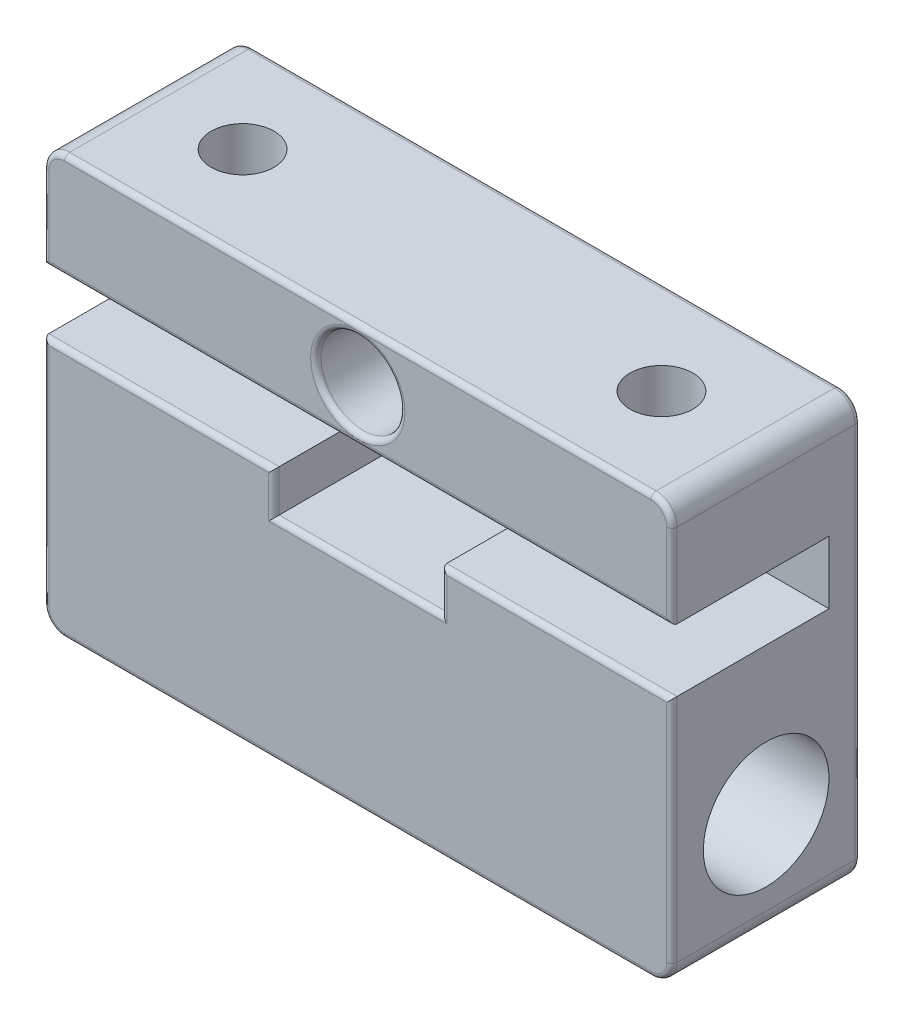
SolidWorks part; units mm, degrees
ref_plane "Front Plane" through (0, 0, 0) normal (0, 0, 1) x (1, 0, 0)
ref_plane "Top Plane" through (0, 0, 0) normal (0, 1, 0) x (1, 0, 0)
ref_plane "Right Plane" through (0, 0, 0) normal (1, 0, 0) x (0, 0, -1)
sketch "Sketch1" plane through (0, 0, 0) normal (0, 0, 1) x (1, 0, 0)
  line L1 (-30, 20) -> (30, 20)
  line L2 (-30, 20) -> (-30, -20)
  line L3 (-30, -20) -> (30, -20)
  line L4 (30, 20) -> (30, -20)
  line L5 (-30, 20) -> (30, -20) construction
  line L6 (-30, -20) -> (30, 20) construction
  point P0 (0, 0)
  dimension "D1" = 40
  dimension "D2" = 60
extrude "Boss-Extrude1" add sketch "Sketch1" along normal mid plane 18
sketch "Sketch2" plane through (-30, 0, 0) normal (-1, 0, 0) x (0, 0, 1)
  line L0 (0, 1.8022) -> (0, -4.9662) construction
  circle A0 centre (0, -10) radius 6
  dimension "D1" = 12
  dimension "D2" = 10
extrude "Cut-Extrude1" cut sketch "Sketch2" against normal through all
sketch "Sketch3" plane through (0, 0, 9) normal (0, 0, 1) x (1, 0, 0)
  line L0 (0, 0) -> (0, 7.3584) construction
  line L4 (30, -20) -> (30, 20)
  line L6 (30, -20) -> (30, 20)
  line L12 (30, 20) -> (-30, 20)
  line L15 (30, 20) -> (-30, 20)
  line L16 (-30, 20) -> (-30, -20)
  line L17 (-30, 20) -> (-30, -20)
  line L18 (-30, -20) -> (30, -20)
  line L19 (-30, -20) -> (30, -20)
  circle A0 centre (0, 15) radius 4
  dimension "D2" = 8
  dimension "D3" = 15
  dimension "D1" = 0
extrude "Cut-Extrude2" cut sketch "Sketch3" against normal through all contours A0 | A0 region at (0, 15, 9)
sketch "Sketch4" plane through (0, 0, 9) normal (0, 0, 1) x (1, 0, 0)
  line L0 (-30, 20) -> (-30, -20) construction
  line L1 (-30, 10) -> (30, 10)
  line L2 (-30, 10) -> (-30, 4)
  line L3 (-30, 4) -> (-8, 4)
  line L4 (30, 10) -> (30, 4)
  line L5 (30, -20) -> (30, 20) construction
  line L6 (8, 4) -> (30, 4)
  line L8 (-8, 4) -> (-8, 0)
  line L9 (-8, 0) -> (8, 0)
  line L10 (8, 4) -> (8, 0)
  dimension "D1" = 6
  dimension "D2" = 16
  dimension "D3" = 8
  dimension "D4" = 10
  dimension "D5" = 4
extrude "Cut-Extrude3" cut sketch "Sketch4" against normal blind 15
sketch "Sketch5" plane through (-30, 0, 0) normal (-1, 0, 0) x (0, 0, 1)
  line L0 (9, 20) -> (9, 10) construction
  line L1 (9, 20) -> (-9, 20) construction
  circle A0 centre (-6, 17) radius 1
  dimension "D1" = 2
  dimension "D2" = 15
  dimension "D3" = 3
extrude "Cut-Extrude4" cut sketch "Sketch5" against normal blind 29
sketch "Sketch6" plane through (-30, 0, 0) normal (-1, 0, 0) x (0, 0, 1)
  circle A0 centre (-6, 17) radius 1.5
  dimension "D1" = 3
extrude "Cut-Extrude5" cut sketch "Sketch6" against normal blind 5
sketch "Sketch7" plane through (0, 20, 0) normal (0, 1, 0) x (1, 0, 0)
  line L0 (-7.4904, 0) -> (6.3865, 0) construction
  line L1 (0, 5.874) -> (0, -4.849) construction
  circle A0 centre (-20, 0) radius 2
  circle A1 centre (20, 0) radius 2
  dimension "D1" = 4
  dimension "D2" = 20
extrude "Cut-Extrude6" cut sketch "Sketch7" against normal up to next
sketch "Sketch8" plane through (0, 20, 0) normal (0, 1, 0) x (1, 0, 0)
  line L0 (0, 5.0067) -> (0, -4.6125) construction
  circle A0 centre (-20, 0) radius 3
  circle A1 centre (20, 0) radius 3
  dimension "D1" = 6
extrude "Cut-Extrude7" cut sketch "Sketch8" against normal blind 5
fillet "Fillet1" radius 2 4 edges at (30, -20, 0) (30, 20, 0) (-30, -20, 0) (-30, 20, 0)
fillet "Fillet2" radius 0.5 26 edges at (29.4142, 19.4142, -9) (0, 20, -9) (4, 15, -9) (-29.4142, 19.4142, -9) (-30, 0, -9) (-29.4142, -19.4142, -9) (0, -20, -9) (29.4142, -19.4142, -9) (30, 0, -9) (-29.4142, -19.4142, 9) (-30, -7, 9) (-19, 4, 9) (-8, 2, 9) (0, 0, 9) (8, 2, 9) (19, 4, 9) (30, -7, 9) (29.4142, -19.4142, 9) (0, -20, 9) (0, 10, 9) (-30, 14, 9) (-29.4142, 19.4142, 9) (0, 20, 9) (4, 15, 9) (29.4142, 19.4142, 9) (30, 14, 9)
